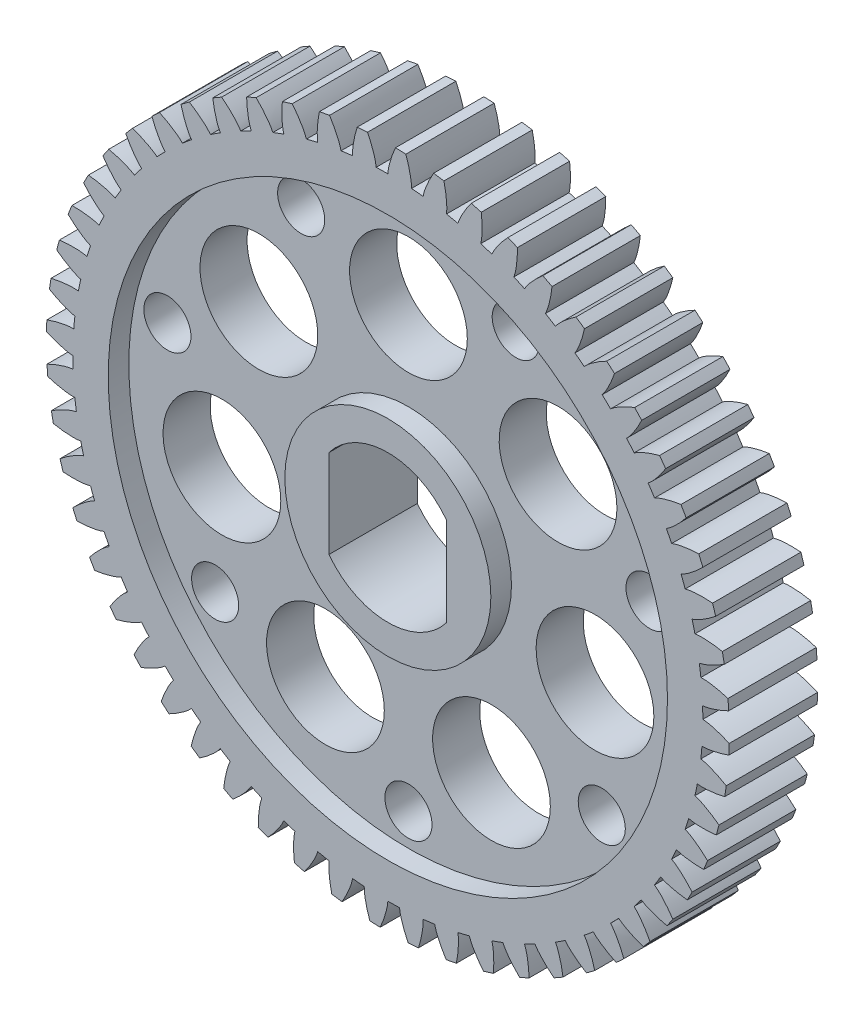
SolidWorks part; units mm, degrees
ref_plane "Front Plane" through (0, 0, 0) normal (0, 0, 1) x (1, 0, 0)
ref_plane "Top Plane" through (0, 0, 0) normal (0, 1, 0) x (1, 0, 0)
ref_plane "Right Plane" through (0, 0, 0) normal (1, 0, 0) x (0, 0, -1)
sketch "Sketch1" plane through (0, 0, 0) normal (0, 0, 1) x (1, 0, 0)
  line L0 (0, 53.5) -> (6.2722, 53.1311) construction
  line L1 (6.2722, 53.1311) -> (12.4578, 52.0293) construction
  line L2 (12.4578, 52.0293) -> (18.4716, 50.21) construction
  line L3 (18.4716, 50.21) -> (24.2307, 47.6982) construction
  line L4 (24.2307, 47.6982) -> (29.6556, 44.5286) construction
  line L5 (6.2722, 53.1311) -> (0.0325, 53.8677) construction
  line L6 (12.4578, 52.0293) -> (0.2372, 54.9554) construction
  line L7 (18.4716, 50.21) -> (0.7818, 56.7179) construction
  line L8 (24.2307, 47.6982) -> (1.8241, 59.0808) construction
  line L9 (29.6556, 44.5286) -> (3.5086, 61.9422) construction
  line L10 (0.5328, 55.9975) -> (3.6721, 55.8795) construction
  line L11 (2.1025, 55.9385) -> (0, 0) construction
  line L12 (0, 53.5) -> (0, 0)
  line L13 (0, 0) -> (4.016, 53.3491)
  circle A0 centre (0, 0) radius 58
  circle A1 centre (0, 0) radius 56 construction
  circle A2 centre (0, 0) radius 53.5 construction
  circle A4 centre (0, 0) radius 53.5
  spline S0 degree 3 poles (0, 53.5) (0.0281, 53.9917) (0.2352, 55.0834) (1.162, 58.0207) (2.4262, 60.3047) (3.5086, 61.9422) knots 0 0 0 0 0.160018 0.360015 1 1 1 1
  spline S1 degree 3 poles (4.016, 53.3491) (4.0249, 53.8415) (3.9003, 54.9457) (3.1967, 57.9442) (2.1075, 60.3167) (1.151, 62.0309) knots 0 0 0 0 0.160018 0.360015 1 1 1 1
  dimension "D1" = 116
  dimension "D2" = 112
  dimension "D3" = 107
  dimension "D4" = 6.283
  dimension "D5" = 6.283
  dimension "D6" = 12.566
  dimension "D7" = 18.849
  dimension "D8" = 25.132
  dimension "D9" = 31.415
  dimension "D10" = 3.1415
extrude "Boss-Extrude1" add sketch "Sketch1" along normal blind 15 contours L12 A4 L13 | L13 A4 L12 | A4 S1 A0 S0 region at (1.3393, 35.6331, 0) region at (2.0832, 55.4263, 0) region at (-0.0162, -0.4313, 0)
pattern_circular "CirPattern1" count 56 over 360 about axis through (0, 0, 15) along (0, 0, 1) of "Boss-Extrude1"
sketch "Sketch2" plane through (0, 0, 15) normal (0, 0, 1) x (1, 0, 0)
  circle A0 centre (0, 0) radius 47.5
  dimension "D1" = 95
extrude "Cut-Extrude1" cut sketch "Sketch2" against normal blind 3.5
extrude "Cut-Extrude2" cut sketch "Sketch2<2>" along normal blind 3.5 from surface starting at face at (0, 0, 0)
sketch "Sketch2<2>" plane through (0, 0, 15) normal (0, 0, 1) x (1, 0, 0) same geometry as "Sketch2"
sketch "Sketch3" plane through (0, 0, 11.5) normal (0, 0, 1) x (1, 0, 0)
  circle A0 centre (0, 0) radius 17.5
  dimension "D1" = 35
extrude "Boss-Extrude2" add sketch "Sketch3" along normal blind 3.5 and the other way blind 11.5
sketch "Sketch4" plane through (0, 0, 15) normal (0, 0, 1) x (1, 0, 0)
  line L0 (0, 9.4423) -> (0, -9.3766) construction
  line L1 (-10, 7.5) -> (-10, -7.5)
  line L2 (10, 7.5) -> (10, -7.5)
  arc A0 (-10, -7.5) -> (10, -7.5) centre (0, 0) ccw
  arc A1 (10, 7.5) -> (-10, 7.5) centre (0, 0) ccw
  dimension "D1" = 25
  dimension "D2" = 20
extrude "Cut-Extrude3" cut sketch "Sketch4" against normal through all
sketch "Sketch5" plane through (0, 0, 11.5) normal (0, 0, 1) x (1, 0, 0)
  circle A0 centre (0, 0) radius 32.5 construction
  circle A1 centre (0, 32.5) radius 10
  dimension "D1" = 65
  dimension "D2" = 20
extrude "Cut-Extrude4" cut sketch "Sketch5" against normal up to next
pattern_circular "CirPattern2" count 7 over 360 about axis through (0, 0, 11.5) along (0, 0, 1) of "Cut-Extrude4"
sketch "Sketch6" plane through (0, 0, 11.5) normal (0, 0, 1) x (1, 0, 0)
  line L0 (4.3388, 41.5097) -> (29.7484, 29.2731) construction
  line L1 (0, 0) -> (17.0436, 35.3914) construction
  line L2 (17.0436, 35.3914) -> (18.2231, 37.8407)
  circle A0 centre (0, 0) radius 42 construction
  circle A1 centre (0, 32.5) radius 10 construction
  circle A2 centre (25.4095, 20.2634) radius 10 construction
  circle A3 centre (18.2231, 37.8407) radius 4
  dimension "D1" = 84
  dimension "D2" = 8
extrude "Cut-Extrude5" cut sketch "Sketch6" against normal up to next contours A3 region at (14.3363, 37.8407, 11.5)
pattern_circular "CirPattern3" count 7 over 360 about axis through (0, 0, 0) along (0, 0, 1) of "Cut-Extrude5"
